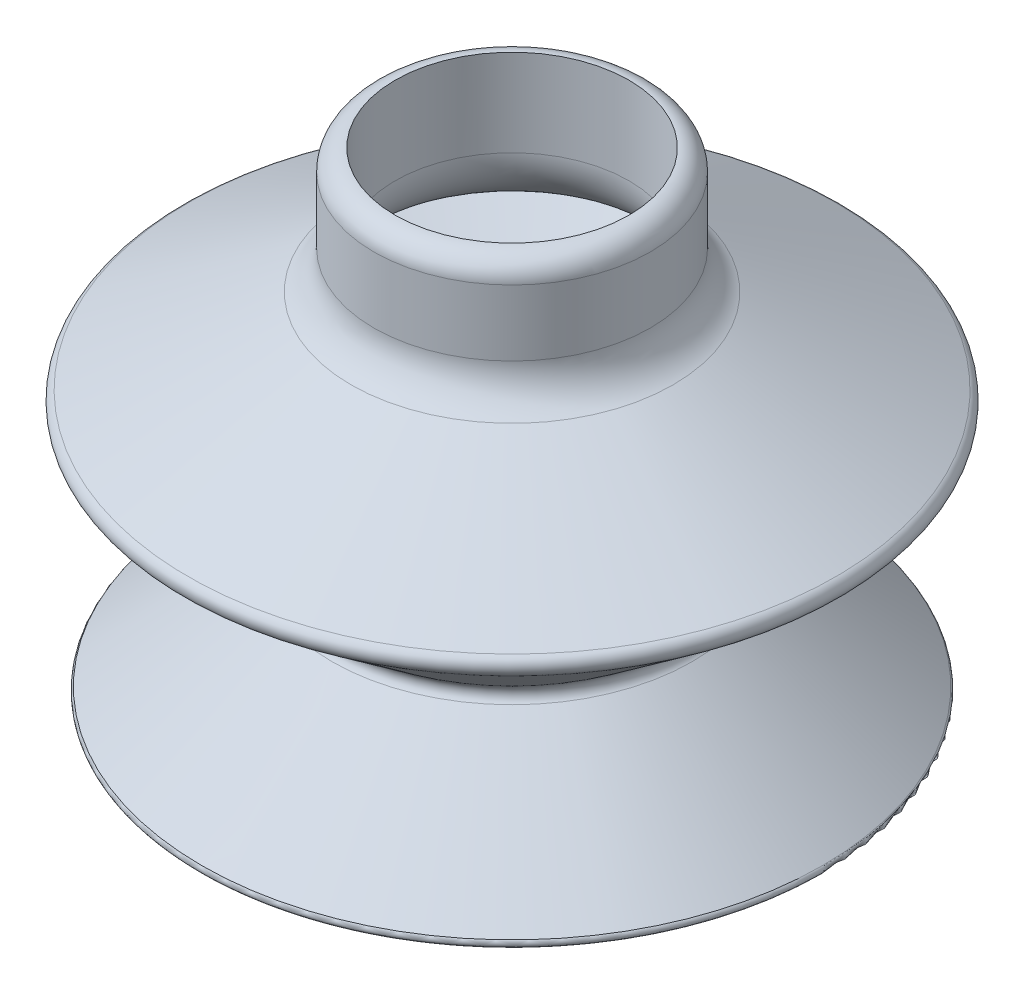
SolidWorks part; units mm, degrees
material "201 Annealed Stainless Steel (SS)"
ref_plane "Front Plane" through (0, 0, 0) normal (0, 0, 1) x (1, 0, 0)
ref_plane "Top Plane" through (0, 0, 0) normal (0, 1, 0) x (1, 0, 0)
ref_plane "Right Plane" through (0, 0, 0) normal (1, 0, 0) x (0, 0, -1)
sketch "Sketch1" plane through (0, 0, 0) normal (0, 0, 1) x (1, 0, 0)
  line L0 (0, 0) -> (0, 32.0237) construction
  line L1 (13.4634, 0) -> (7.8172, 4.8396)
  line L2 (7.8804, 7.1686) -> (14.073, 11.919)
  line L3 (15, 0) -> (8.468, 5.5988)
  line L4 (8.4891, 6.3752) -> (15.3043, 11.6033)
  line L5 (15.2309, 12.4435) -> (7.5763, 16.4295)
  line L6 (6.5, 18.2034) -> (6.5, 22.3)
  line L7 (6.5, 22.3) -> (0, 22.3)
  line L8 (14.073, 11.919) -> (7.1144, 15.5426)
  line L9 (5.5, 18.2034) -> (5.5, 21.3)
  line L10 (5.5, 21.3) -> (0, 21.3)
  line L11 (15, 0) -> (13.4634, 0)
  line L12 (14.3492, -0.7593) -> (7.8172, 4.8396) construction
  line L13 (0, 22.3) -> (0, 21.3)
  arc A0 (15.3043, 11.6033) -> (15.2309, 12.4435) centre (15, 12) ccw
  arc A1 (8.4891, 6.3752) -> (8.468, 5.5988) centre (8.7934, 5.9785) ccw
  arc A2 (7.5763, 16.4295) -> (6.5, 18.2034) centre (8.5, 18.2034) cw
  arc A3 (7.8804, 7.1686) -> (7.8172, 4.8396) centre (8.7934, 5.9785) ccw
  arc A4 (14.073, 11.919) -> (14.073, 11.919) centre (14.073, 11.919) ccw
  arc A5 (7.1144, 15.5426) -> (5.5, 18.2034) centre (8.5, 18.2034) cw
  point P28 (8, 6)
  dimension "D3" = 0.5
  dimension "D9" = 0.5
  dimension "D10" = 2
  dimension "D1" = 15
  dimension "D2" = 12
  dimension "D4" = 6
  dimension "D5" = 8
  dimension "D6" = 22.3
  dimension "D7" = 6.5
  dimension "D8" = 65
  dimension "D11" = 1
revolve "Revolve1" add sketch "Sketch1" angle 360 about L0
fillet "Fillet1" radius 1 1 edges at (0, 22.3, -6.5)
fillet "Fillet2" radius 0.2 2 edges at (0, 0, -13.4634) (0, 0, -15)
sketch "Sketch2" plane through (0, 22.3, 0) normal (0, 1, 0) x (1, 0, 0)
  line L1 (6.5, 0) -> (3.25, 5.6292)
  line L2 (3.25, 5.6292) -> (-3.25, 5.6292)
  line L3 (-3.25, 5.6292) -> (-6.5, 0)
  line L4 (-6.5, 0) -> (-3.25, -5.6292)
  line L5 (-3.25, -5.6292) -> (3.25, -5.6292)
  line L6 (3.25, -5.6292) -> (6.5, 0)
  circle A0 centre (0, 0) radius 5.6292 construction
  dimension "D1" = 6.5
extrude "Boss-Extrude1" add sketch "Sketch2" along normal blind 5
fillet "Fillet3" radius 0.5 18 edges at (4.875, 22.3, 2.8146) (4.875, 22.3, -2.8146) (0, 22.3, -5.6292) (-4.875, 22.3, -2.8146) (-4.875, 22.3, 2.8146) (4.875, 27.3, -2.8146) (0, 27.3, -5.6292) (-4.875, 27.3, -2.8146) (-4.875, 27.3, 2.8146) (3.25, 24.8, 5.6292) (-3.25, 24.8, 5.6292) (-6.5, 24.8, 0) (-3.25, 24.8, -5.6292) (3.25, 24.8, -5.6292) (6.5, 24.8, 0) (0, 22.3, 5.6292) (4.875, 27.3, 2.8146) (0, 27.3, 5.6292)
sketch "Sketch3" plane through (0, 27.3, 0) normal (0, 1, 0) x (1, 0, 0)
  circle A0 centre (0, 0) radius 4.35
  dimension "D1" = 8.7
extrude "Boss-Extrude2" add sketch "Sketch3" along normal blind 6.2
sketch "Sketch4" plane through (0, 33.5, 0) normal (0, 1, 0) x (1, 0, 0)
  circle A0 centre (0, 0) radius 1.5
  dimension "D1" = 3
extrude "Cut-Extrude1" cut sketch "Sketch4" against normal through all both and the other way through all
thread "Thread1" pitch 0.8 method extrude profile "Thread Profile1" start angle 0, offset 0, length 11, pitch 0.8, diameter 8.7
ref_plane "Plane1" through (-4.35, 33.5, 0) normal (0, 0, 1) x (-1, 0, 0)
sketch "Thread Profile1" plane through (-4.35, 33.5, 0) normal (0, 0, 1) x (-1, 0, 0)
  line L0 (0, 0) -> (0, 0.8) construction
  line L1 (0, 0) -> (0.433, 0.25)
  line L2 (0.433, 0.25) -> (0.433, 0.35)
  line L3 (0.433, 0.35) -> (0, 0.6)
  line L4 (0.433, 0.3) -> (0, 0.3) construction
  line L11 (0, 0) -> (0, 0.6)
  point P2 (0, 0)
  dimension "Pitch" = 0.8
  dimension "Profile_Angle" = 60
  dimension "Profile_Land" = 0.1
  dimension "Profile_Height" = 0.433
sketch "Sketch6" plane through (0, 27.3, 0) normal (0, 1, 0) x (1, 0, 0)
  circle A0 centre (0, 0) radius 5.1
  circle A1 centre (0, 0) radius 1.5
  dimension "D1" = 10.2
  dimension "D2" = 3
extrude "Boss-Extrude3" add sketch "Sketch6" along normal blind 1.5
sketch "Sketch7" plane through (0, 33.5, 0) normal (0, 1, 0) x (1, 0, 0)
  circle A0 centre (0, 0) radius 7.5763
extrude "Cut-Extrude2" cut sketch "Sketch7" against normal up to surface (11.2 mm away) body kept at (5.4347, 22.3, -0.8452) up to face at (-2.8096, 22.3, 4.8663)
sketch "Sketch8" plane through (0, 22.3, 0) normal (0, 1, 0) x (1, 0, 0)
  circle A0 centre (0, 0) radius 5.5
extrude "Cut-Extrude3" cut sketch "Sketch8" against normal through all
